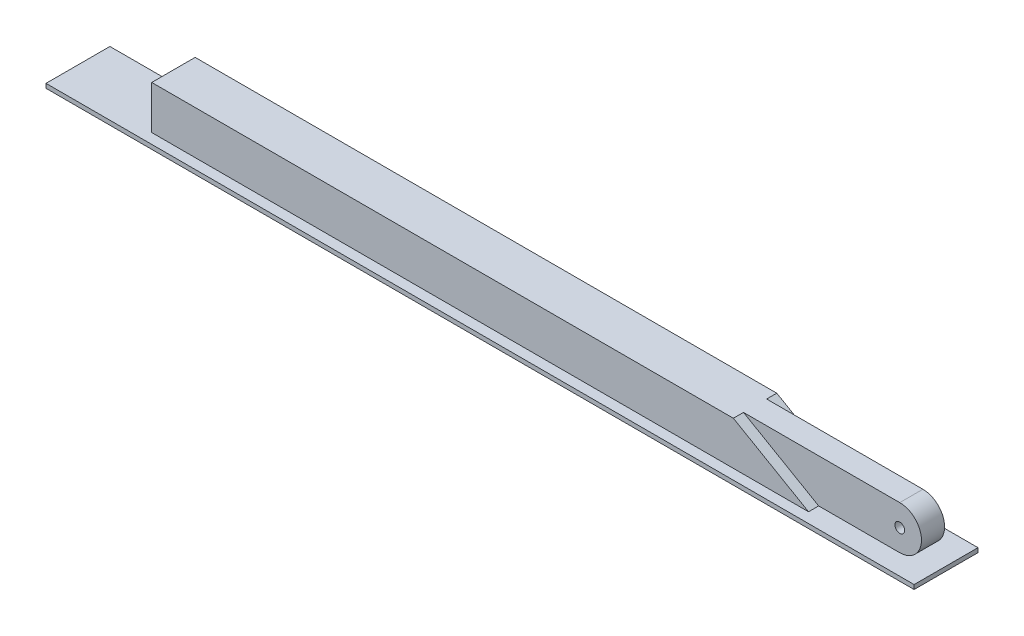
SolidWorks part; units mm, degrees
ref_plane "Front Plane" through (0, 0, 0) normal (0, 0, 1) x (1, 0, 0)
ref_plane "Top Plane" through (0, 0, 0) normal (0, 1, 0) x (1, 0, 0)
ref_plane "Right Plane" through (0, 0, 0) normal (1, 0, 0) x (0, 0, -1)
sketch "Sketch1" plane through (0, 0, 0) normal (0, 0, 1) x (1, 0, 0)
  line L0 (-225, 0) -> (225, 0) construction
  line L1 (-225, 15) -> (225, 15)
  line L2 (-225, -15) -> (225, -15)
  arc A0 (-225, 15) -> (-225, -15) centre (-225, 0) ccw
  arc A1 (225, -15) -> (225, 15) centre (225, 0) ccw
  point P2 (0, 0)
  dimension "D1" = 450
  dimension "D2" = 30
extrude "Boss-Extrude1" add sketch "Sketch1" along normal mid plane 30
hole_wizard "H (0.266) Diameter Hole1" positions "Sketch2" profile "Sketch4" hole size "H" standard "ANSI Inch" end condition through all
sketch "Sketch2" plane through (0, 0, 15) normal (0, 0, 1) x (1, 0, 0)
  point P0 (-225, 0)
  point P3 (225, 0)
sketch "Sketch4" plane through (-225, 0, 15) normal (1, 0, 0) x (0, -1, 0)
  line L0 (0, 0) -> (0, 30)
  line L1 (0, 30) -> (3.3782, 30)
  line L2 (3.3782, 30) -> (3.3782, 0)
  line L5 (3.3782, 0) -> (0, 0)
  line L11 (0, -6.35) -> (0, 107.95) construction
  dimension "Thru Hole Dia." = 6.7564
  dimension "Thru Hole Depth" = 30
sketch "Sketch5" plane through (0, 15, 0) normal (0, 1, 0) x (1, 0, 0)
  line L1 (-257, 8) -> (-217, 8)
  line L2 (-257, 8) -> (-257, -8)
  line L3 (-257, -8) -> (-217, -8)
  line L4 (-217, 8) -> (-217, -8)
  line L5 (-217, 0) -> (0, 0) construction
  line L6 (-225, -15) -> (-225, 15) construction
  line L7 (225, -15) -> (225, 15) construction
  line L8 (217, 28.9161) -> (257, 28.9161)
  line L9 (217, 28.9161) -> (217, 8)
  line L10 (217, 8) -> (257, 8)
  line L11 (257, 28.9161) -> (257, 8)
  line L12 (217, -28.9161) -> (257, -28.9161)
  line L13 (217, -28.9161) -> (217, -8)
  line L14 (217, -8) -> (257, -8)
  line L15 (257, -28.9161) -> (257, -8)
  dimension "D1" = 16
  dimension "D2" = 8
  dimension "D3" = 40
  dimension "D4" = 8
extrude "Cut-Extrude1" cut sketch "Sketch5" against normal through all
sketch "Sketch6" plane through (0, 15, 0) normal (0, 1, 0) x (1, 0, 0)
  line L0 (217, 15) -> (217, 8) construction
  line L1 (-262.0368, 59.0418) -> (167, 59.0418)
  line L2 (-262.0368, 59.0418) -> (-262.0368, -68.39)
  line L3 (-262.0368, -68.39) -> (167, -68.39)
  line L4 (167, 59.0418) -> (167, -68.39)
  dimension "D1" = 50
extrude "Cut-Extrude2" cut sketch "Sketch6" against normal through all
sketch "Sketch10" plane through (167, 0, 0) normal (-1, 0, 0) x (0, 0, 1)
  line L1 (15, -15) -> (-15, -15)
  line L2 (15, -15) -> (15, 15)
  line L3 (15, 15) -> (-15, 15)
  line L4 (-15, -15) -> (-15, 15)
  line L5 (15, -15) -> (-15, 15) construction
  line L6 (15, 15) -> (-15, -15) construction
  point P0 (0, 0)
extrude "Boss-Extrude3" add sketch "Sketch10" along normal blind 500
sketch "Sketch11" plane through (-333, 0, 0) normal (-1, 0, 0) x (0, 0, 1)
  line L0 (8, -15) -> (-8, -15) construction
  circle A0 centre (0, 3) radius 9.525
  dimension "D1" = 19.05
  dimension "D2" = 18
extrude "Cut-Extrude4" cut sketch "Sketch11" against normal blind 400
sketch "Sketch13" plane through (0, -15, 0) normal (0, -1, 0) x (-1, 0, 0)
  line L0 (327.115, -22.0795) -> (327.115, 22.0795) construction
  line L1 (351, -22.0795) -> (-249, -22.0795)
  line L2 (351, -22.0795) -> (351, 22.0795)
  line L3 (351, 22.0795) -> (-249, 22.0795)
  line L4 (-249, -22.0795) -> (-249, 22.0795)
  line L5 (333, 15) -> (333, -15) construction
  line L8 (-249, 0) -> (0, 0) construction
  point P0 (0, 0)
  dimension "D1" = 600
  dimension "D2" = 18
extrude "Boss-Extrude4" add sketch "Sketch13" along normal blind 3
sketch "Sketch14" plane through (0, 15, 0) normal (0, 1, 0) x (1, 0, 0)
  line L0 (225, -8) -> (225, 8) construction
  line L1 (-396.0349, 53.7915) -> (-285, 53.7915)
  line L2 (-396.0349, 53.7915) -> (-396.0349, -58.394)
  line L3 (-396.0349, -58.394) -> (-285, -58.394)
  line L4 (-285, 53.7915) -> (-285, -58.394)
  dimension "D1" = 510
extrude "Cut-Extrude5" cut sketch "Sketch14" against normal up to surface (30 mm away) up to face at (-51, -15, 0)
chamfer "Chamfer1" distance 100 angle 30 2 edges at (217, 15, -11.5) (217, 15, 11.5) first distance on face at (93.5, 15, 0)
